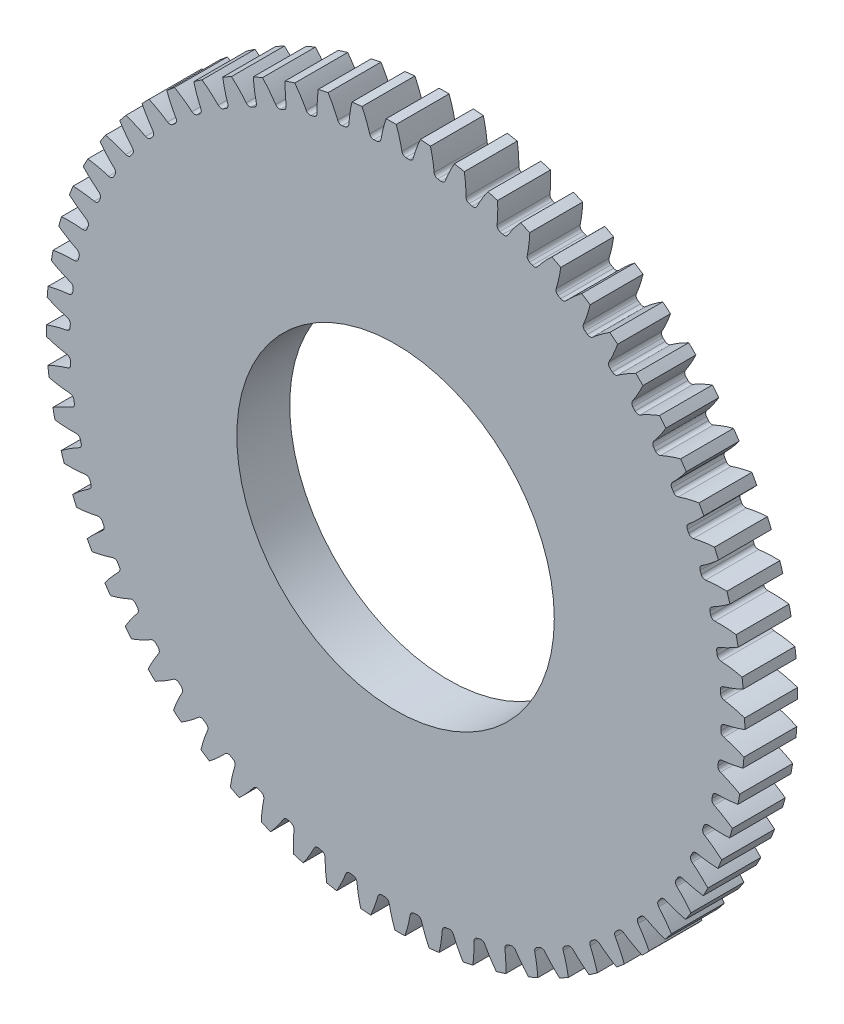
SolidWorks part; units mm, degrees
ref_plane "Front" through (0, 0, 0) normal (0, 0, 1) x (1, 0, 0)
ref_plane "Top" through (0, 0, 0) normal (0, 1, 0) x (1, 0, 0)
ref_plane "Right" through (0, 0, 0) normal (1, 0, 0) x (0, 0, -1)
sketch "Sketch3" plane through (0, 0, 0) normal (0, 0, 1) x (1, 0, 0)
  circle A0 centre (0, 0) radius 41.91
  dimension "od" = 83.82
extrude "gearBody" add sketch "Sketch3" along normal blind 6.35
sketch "Sketch2" plane through (0, 0, 0) normal (0, 0, 1) x (1, 0, 0)
  line L0 (0, 0) -> (36.3505, 15.0569) construction
  line L1 (49.1027, -9.5876) -> (0, 0) construction
  line L2 (0, 0) -> (36.3143, 0) construction
  line L3 (40.6371, -0.4885) -> (40.564, -2.485) construction
  line L5 (40.6005, -1.4868) -> (0, 0) construction
  line L7 (0, 0) -> (39.3455, 0) construction
  arc A0 (39.3376, -0.7896) -> (39.29, -2.0897) centre (0, 0) ccw construction
  arc A1 (41.9099, -0.0801) -> (41.8035, -2.9854) centre (0, 0) ccw construction
  arc A2 (40.6371, -0.4885) -> (40.564, -2.485) centre (0, 0) ccw construction
  arc A3 (39.0317, -1.6169) -> (39.0454, -1.2423) centre (0, 0) ccw
  arc A4 (49.1027, -9.5876) -> (39.399, -2.119) centre (35.1519, -17.6753) ccw
  arc A5 (49.1027, -9.5876) -> (49.6724, 5.9705) centre (0, 0) ccw
  arc A6 (49.6724, 5.9705) -> (39.4484, -0.7683) centre (36.3505, 15.0569) cw
  arc A7 (39.0454, -1.2423) -> (39.4484, -0.7683) centre (39.5443, -1.2582) cw
  arc A8 (39.399, -2.119) -> (39.0317, -1.6169) centre (39.5304, -1.6375) cw
  point P6 (49.6724, 5.9705)
  point P22 (49.1027, -9.5876)
  dimension "baseDia" = 78.691
  dimension "od" = 83.82
  dimension "pd" = 81.28
  dimension "rd" = 78.1304
  dimension "rFillet" = 0.4991
  dimension "pointX" = 49.6724
  dimension "pointY" = 5.9705
  dimension "CTT" = 1.9964
  dimension "flankCenterAngle" = 22.5
extrude "toothCut" cut sketch "Sketch2" along normal through all
pattern_circular "CirPattern1" count 64 over 360 about axis through (0, 0, 6.35) along (0, 0, -1) of "toothCut"
sketch "hub1Dia" plane through (0, 0, 0) normal (0, 0, -1) x (-1, 0, 0)
  circle A0 centre (0, 0) radius 25.4
  dimension "hub1Dia" = 50.8
extrude "hub1" [suppressed] add sketch "hub1Dia" along normal blind 19.05
sketch "hub2Dia" plane through (0, 0, 6.35) normal (0, 0, 1) x (1, 0, 0)
  circle A0 centre (0, 0) radius 21.844
  dimension "hub2dia" = 43.688
extrude "hub2" [suppressed] add sketch "hub2Dia" along normal blind 16.002
sketch "boreDia" plane through (0, 0, 0) normal (0, 0, 1) x (1, 0, 0)
  circle A0 centre (0, 0) radius 19.05
  dimension "boreDia" = 38.1
extrude "bore" cut sketch "boreDia" against normal mid plane 25400
chamfer "hub2Chamfer" [suppressed] distance 0.508 angle 45
chamfer "hub2BoreChamfer" [suppressed] distance 0.508 angle 45
chamfer "hub1BoreChamfer" [suppressed] distance 0.508 angle 45
chamfer "hub1Chamfer" [suppressed] distance 0.508 angle 45
chamfer "BoreChamfer2" [suppressed] distance 0.508 angle 45
chamfer "boreChamfer1" [suppressed] distance 0.508 angle 45
